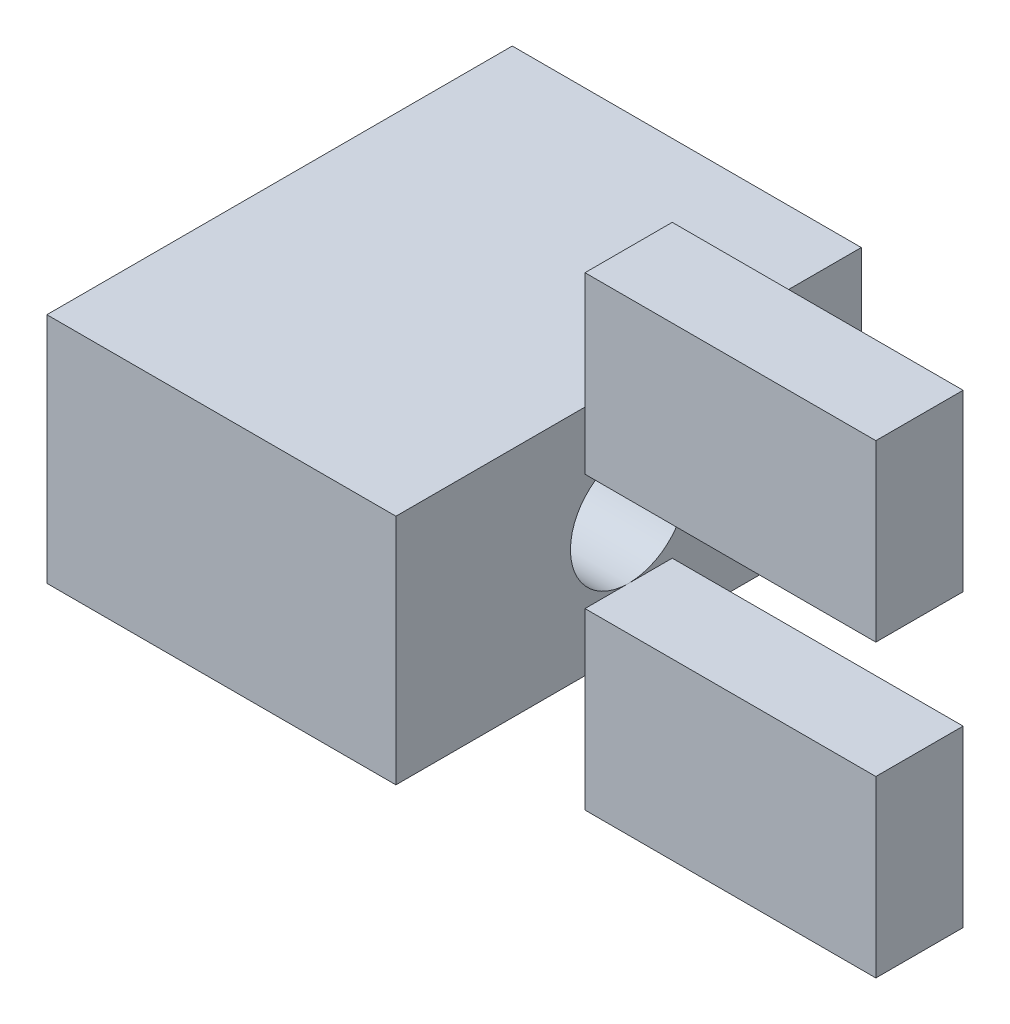
SolidWorks part; units mm, degrees
ref_plane "前视基准面" through (0, 0, 0) normal (0, 0, 1) x (1, 0, 0)
ref_plane "上视基准面" through (0, 0, 0) normal (0, 1, 0) x (1, 0, 0)
ref_plane "右视基准面" through (0, 0, 0) normal (1, 0, 0) x (0, 0, -1)
other "Configuration Table"
sketch "Sketch1" plane through (0, 0, 0) normal (1, 0, 0) x (0, 0, -1)
  line L1 (-40, -20) -> (40, -20)
  line L2 (-40, -20) -> (-40, 20)
  line L3 (-40, 20) -> (40, 20)
  line L4 (40, -20) -> (40, 20)
  line L5 (-40, -20) -> (40, 20) construction
  line L6 (-40, 20) -> (40, -20) construction
  point P0 (0, 0)
extrude "Boss-Extrude1" add sketch "Sketch1" along normal blind 60
sketch "Sketch2" plane through (0, 0, 0) normal (1, 0, 0) x (0, 0, -1)
  circle A0 centre (0, 0) radius 10
extrude "Cut-Extrude1" cut sketch "Sketch2" along normal blind 60
ref_plane "Plane1" through (60, 0, 0) normal (1, 0, 0) x (0, 0, -1)
sketch "Sketch3" plane through (60, 0, 0) normal (1, 0, 0) x (0, 0, -1)
  line L1 (-7.5, 10) -> (7.5, 10)
  line L2 (-7.5, 10) -> (-7.5, 40)
  line L3 (-7.5, 40) -> (7.5, 40)
  line L4 (7.5, 10) -> (7.5, 40)
  line L5 (-7.5, 10) -> (7.5, 40) construction
  line L6 (-7.5, 40) -> (7.5, 10) construction
  line L7 (-7.5, -40) -> (7.5, -40)
  line L8 (-7.5, -40) -> (-7.5, -10)
  line L9 (-7.5, -10) -> (7.5, -10)
  line L10 (7.5, -40) -> (7.5, -10)
  line L11 (-7.5, -40) -> (7.5, -10) construction
  line L12 (-7.5, -10) -> (7.5, -40) construction
  point P0 (0, 25)
  point P5 (0, -25)
extrude "Boss-Extrude2" add sketch "Sketch3" along normal blind 50
ref_plane "mid_plane_y" through (0, 0, 0) normal (0, 1, 0) x (1, 0, 0)
sketch3d "3DSketch1"
  line L0 (0, 0, 0) -> (0, 40, 0) construction
ref_axis "mount_axis_y" through (0, 0, 0) along (0, 1, 0)
